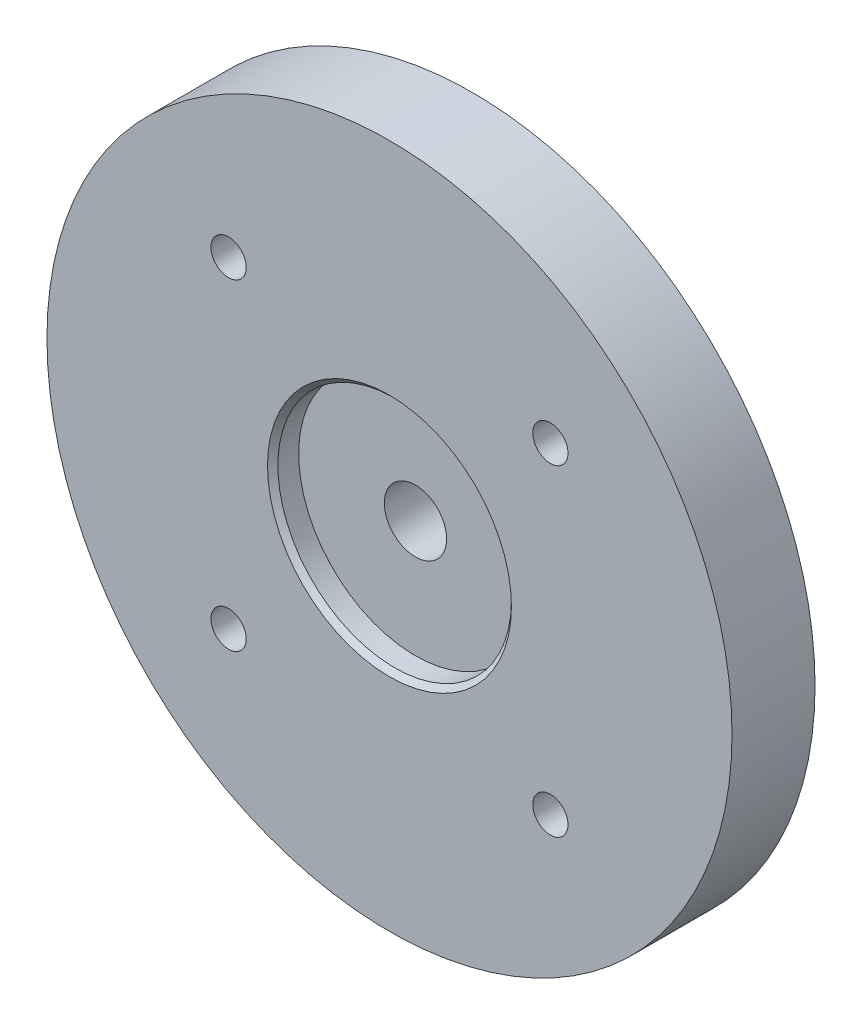
SolidWorks part; units mm, degrees
ref_plane "Front Plane" through (0, 0, 0) normal (0, 0, 1) x (1, 0, 0)
ref_plane "Top Plane" through (0, 0, 0) normal (0, 1, 0) x (1, 0, 0)
ref_plane "Right Plane" through (0, 0, 0) normal (1, 0, 0) x (0, 0, -1)
sketch "Sketch2" plane through (0, 0, 0) normal (0, 0, 1) x (1, 0, 0)
  circle A0 centre (0, 0) radius 33
  dimension "D1" = 66
extrude "Boss-Extrude1" add sketch "Sketch2" along normal blind 8
sketch "Sketch6" plane through (0, 0, 0) normal (0, 0, -1) x (-1, 0, 0)
  circle A0 centre (0, 0) radius 10
  dimension "D1" = 20
extrude "Boss-Extrude2" add sketch "Sketch6" along normal blind 2
sketch "Sketch3" plane through (0, 0, 8) normal (0, 0, 1) x (1, 0, 0)
  line L0 (0, -15.5) -> (0, 15.5) construction
  line L1 (15.5, 15.5) -> (-15.5, 15.5) construction
  line L2 (15.5, -15.5) -> (-15.5, -15.5) construction
  circle A0 centre (-15.5, 15.5) radius 1.7
  circle A1 centre (15.5, 15.5) radius 1.7
  circle A2 centre (15.5, -15.5) radius 1.7
  circle A3 centre (-15.5, -15.5) radius 1.7
  circle A4 centre (0, 0) radius 3
  point P12 (0, 0)
  point P16 (0, 15.5)
  point P19 (0, -15.5)
  dimension "D1" = 3.4
  dimension "D2" = 3.4
  dimension "D3" = 3.4
  dimension "D4" = 3.4
  dimension "D8" = 6
  dimension "D5" = 31
  dimension "D6" = 31
  dimension "D7" = 31
extrude "Cut-Extrude1" cut sketch "Sketch3" against normal through all both and the other way through all
sketch "Sketch4" plane through (0, 0, 0) normal (0, 0, -1) x (-1, 0, 0)
  circle A0 centre (-15.5, 15.5) radius 2.8
  circle A1 centre (15.5, 15.5) radius 2.8
  circle A2 centre (15.5, -15.5) radius 2.8
  circle A3 centre (-15.5, -15.5) radius 2.8
  dimension "D1" = 5.6
  dimension "D2" = 5.6
  dimension "D3" = 5.6
  dimension "D4" = 5.6
extrude "Cut-Extrude2" cut sketch "Sketch4" against normal blind 2 and the other way through all
sketch "Sketch5" plane through (0, 0, 0) normal (0, 0, -1) x (-1, 0, 0)
  circle A0 centre (0, 29.5) radius 2.1
  circle A1 centre (29.5, 0) radius 2.1
  circle A2 centre (0, -29.5) radius 2.1
  circle A3 centre (-29.5, 0) radius 2.1
  point P19 (0, 0)
  dimension "D1" = 4.2
  dimension "D2" = 29.5
  dimension "D3" = 4
extrude "Cut-Extrude3" cut sketch "Sketch5" against normal blind 6
fillet "Fillet1" radius 1 1 edges at (-10, 0, 0)
sketch "Sketch7" plane through (0, 0, 8) normal (0, 0, 1) x (1, 0, 0)
  circle A0 centre (0, 0) radius 11.25
  dimension "D1" = 22.5
extrude "Cut-Extrude4" cut sketch "Sketch7" against normal blind 2.5
chamfer "Chamfer1" distance 0.5 angle 45 1 edges at (11.25, 0, 8)
equation "\"N_pins\"= 26"
equation "\"N_lobes\"= \"N_pins\" - 1"
equation "\"R_pc\"= 25"
equation "\"D_pin\"= 3"
equation "\"R_pin\"= \"D_pin\" / 2"
equation "\"ecc\"= 0.72"
equation "\"t_disc\"= 7"
equation "\"N_out\"= 8"
equation "\"D_outc\"=22"
equation "\"D_roller\"= 5"
equation "\"D_outhole\"= \"D_roller\" + 2 * \"ecc\""
equation "\"D_cam_OD\"= 21"
equation "\"D_cam_ID\"= 10"
equation "\"clr_bore\"= 1"
equation "\"D_bore\"= 2 * \"R_pc\" + \"clr_bore\""
equation "\"t_wall\"= 7.5"
equation "\"D_housing\"= \"D_bore\" + 2 * \"t_wall\""
equation "\"D1@Sketch2\"=\"D_housing\""
